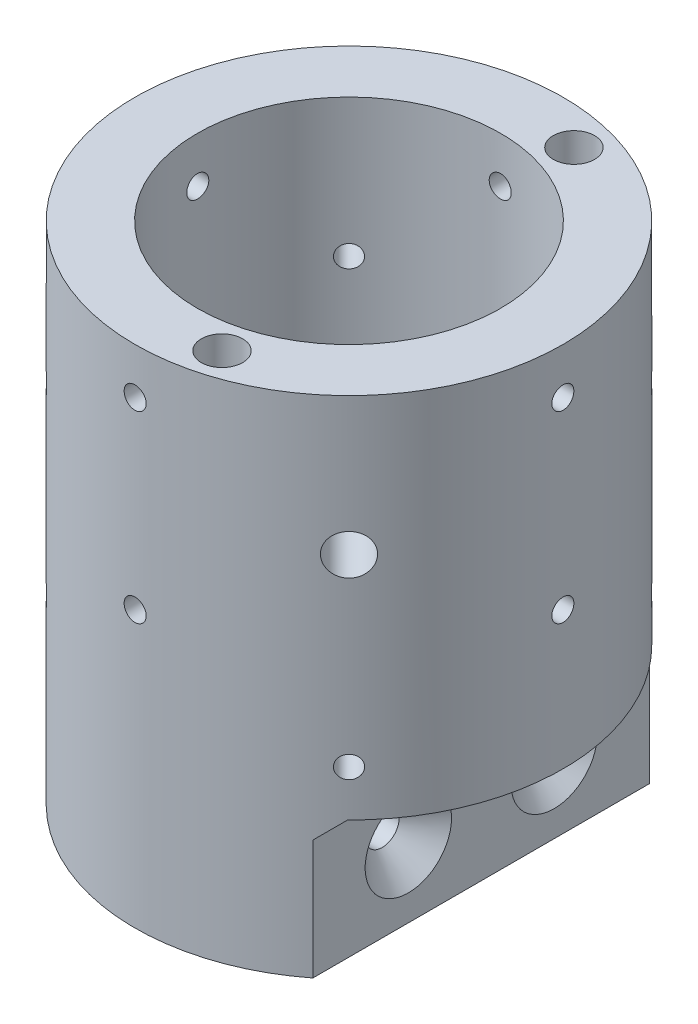
SolidWorks part; units mm, degrees
material "PLA плотность"
ref_plane "Спереди" through (0, 0, 0) normal (0, 0, 1) x (1, 0, 0)
ref_plane "Сверху" through (0, 0, 0) normal (0, 1, 0) x (1, 0, 0)
ref_plane "Справа" through (0, 0, 0) normal (1, 0, 0) x (0, 0, -1)
sketch "Эскиз1" plane through (0, 0, 0) normal (0, 1, 0) x (1, 0, 0)
  circle A0 centre (0, 0) radius 23.3
  dimension "D1" = 46.6
extrude "Бобышка-Вытянуть1" add sketch "Эскиз1" along normal blind 5
sketch "Эскиз2" plane through (0, 5, 0) normal (0, 1, 0) x (1, 0, 0)
  circle A0 centre (0, 0) radius 23.3
  circle A1 centre (0, 0) radius 16.5
  circle A2 centre (0, 0) radius 23.3 construction
  dimension "D1" = 33
  dimension "D2" = 0
extrude "Бобышка-Вытянуть2" add sketch "Эскиз2" along normal blind 35
chamfer "Фаска8" distance 2 angle 45 1 edges at (0, 5, 16.5)
sketch "Эскиз3" plane through (0, 0, 0) normal (1, 0, 0) x (0, 0, -1)
  line L0 (-23.3, 20) -> (28.0263, 20) construction
  line L1 (-23.3, 40) -> (-23.3, 0) construction
  line L2 (16.5, 40) -> (-16.5, 40) construction
  circle A1 centre (0, 35) radius 1.2
  dimension "D1" = 2.4
  dimension "D2" = 5
extrude "Вырез-Вытянуть1" cut sketch "Эскиз3" against normal through all
ref_plane "Плоскость1" through (0, 0, 0) normal (0.7071, 0, 0.7071) x (0, -1, 0)
sketch "Эскиз4" plane through (0, 0, 0) normal (0.7071, 0, 0.7071) x (0, -1, 0)
  line L0 (-20, 23.3) -> (-20, -30.0625) construction
  line L1 (0, 23.3) -> (-40, 23.3) construction
  line L3 (0, -23.3) -> (0, 23.3) construction
  circle A1 centre (-5, 0) radius 1.2
  dimension "D1" = 5
  dimension "D2" = 2.4
extrude "Вырез-Вытянуть2" cut sketch "Эскиз4" against normal through all from offset 16.3 offset against normal yes
pattern_circular "Круговой массив1" count 4 over 360 about axis through (0, 5, 0) along (0, -1, 0) of "Вырез-Вытянуть2"
pattern_circular "Круговой массив2" count 4 over 360 about axis through (0, 5, 0) along (0, -1, 0) of "Вырез-Вытянуть1"
pattern_linear "Линейный массив3" count 2 spacing 20 along (0, 1, 0) of "Круговой массив1"
pattern_linear "Линейный массив4" count 2 spacing 20 along (0, -1, 0) of "Круговой массив2"
sketch "Эскиз12" plane through (0, 0, 0) normal (0, -1, 0) x (1, 0, 0)
  line L1 (14.3923, 18.3235) -> (14.3923, -18.3235)
  line L20 (0, 15) -> (-2.7835, 17.7835)
  line L21 (-2.7835, -17.7835) -> (0, -15)
  line L22 (0, -15) -> (0, 15)
  line L23 (0, 15) -> (-2.7835, 17.7835)
  line L24 (-2.7835, -17.7835) -> (0, -15)
  line L25 (0, -15) -> (0, 15)
  circle A6 centre (0, 0) radius 23.3 construction
  arc A7 (14.3923, 18.3235) -> (14.3923, -18.3235) centre (0, 0) ccw
  arc A13 (-2.7835, 17.7835) -> (-2.7835, -17.7835) centre (0, 0) ccw
  arc A14 (-2.7835, 17.7835) -> (-2.7835, -17.7835) centre (0, 0) ccw
  dimension "D1" = 0
extrude "Бобышка-Вытянуть3" add sketch "Эскиз12" along normal blind 15 contours L1 region at (13.7929, 0, 0)
sketch "Эскиз13" plane through (0, -15, 0) normal (0, -1, 0) x (1, 0, 0)
  line L14 (-2.6786, -18.1029) -> (0.3, -15.1243)
  line L15 (0.3, 15.1243) -> (-2.6786, 18.1029)
  line L16 (0.3, -15.1243) -> (0.3, 15.1243)
  line L17 (-2.6786, -18.1029) -> (0.3, -15.1243)
  line L18 (0.3, 15.1243) -> (-2.6786, 18.1029)
  line L19 (0.3, -15.1243) -> (0.3, 15.1243)
  arc A5 (-2.6786, 18.1029) -> (-2.6786, -18.1029) centre (0, 0) ccw
  arc A6 (-2.6786, 18.1029) -> (-2.6786, -18.1029) centre (0, 0) ccw
  dimension "D1" = 0.3
extrude "Вырез-Вытянуть10" cut sketch "Эскиз13" against normal up to surface (15 mm away) up to face at (18.8461, 0, 0)
chamfer "Фаска4" distance 2 angle 45 1 edges at (14.3923, 0, 0)
chamfer "Фаска6" distance 2 angle 45 4 edges at (-1.1893, 0, -16.6136) (-18.3, 0, 0) (0.3, 0, 0) (-1.1893, 0, 16.6136)
chamfer "Фаска7" distance 2 angle 45 4 edges at (-1.1893, -15, -16.6136) (-18.3, -15, 0) (-1.1893, -15, 16.6136) (0.3, -15, 0)
hole_wizard "Зенковка для винта с полупотайной головкой M41" positions "Эскиз14" profile "Эскиз15" countersink size "M4" standard "ISO" end condition through all
sketch "Эскиз14" plane through (14.3923, -676.2045, -24.0267) normal (1, 0, 0) x (0, -0.1282, -0.9918)
  line L0 (-110.237, 665.565) -> (-108.5708, 652.6722) construction
  line L4 (-109.4039, 659.1186) -> (-20.4413, 659.1186) construction
  line L5 (-20.4413, 659.1186) -> (-1.8045, 659.1186) construction
  point P0 (-117.4039, 659.1186)
  point P19 (-101.6667, 661.1523)
sketch "Эскиз15" plane through (14.3923, -7.4747, 7.934) normal (0, 1, 0) x (0, 0, -1)
  line L0 (0, 0) -> (0, 37.6923)
  line L1 (0, 37.6923) -> (1.85, 37.6923)
  line L2 (1.85, 37.6923) -> (1.85, 2.85)
  line L3 (1.85, 2.85) -> (4.7, 0)
  line L4 (4.7, 0) -> (0, 0)
  line L5 (-1.85, 2.85) -> (-4.7, 0) construction
  line L6 (0, -6.35) -> (0, 107.95) construction
  dimension "Диаметр сквозного отверстия" = 3.7
  dimension "Глубина сквозного отверстия" = 37.6923
  dimension "Диаметр передней зенковки" = 9.4
  dimension "Угол передней зенковки" = 90
sketch "Эскиз17" plane through (0, -15, 0) normal (0, -1, 0) x (1, 0, 0)
  circle A0 centre (5.3288, 0) radius 2.5
extrude "Вырез-Вытянуть11" cut sketch "Эскиз17" against normal blind 86
ref_plane "Плоскость2" through (0, 0, 0) normal (-0.7071, 0, -0.7071) x (-0.7071, 0, 0.7071)
sketch "Эскиз18" plane through (0, 0, 0) normal (-0.7071, 0, -0.7071) x (-0.7071, 0, 0.7071)
  circle A0 centre (0, 25) radius 1.2 construction
  circle A1 centre (0, 25) radius 1.2
  circle A2 centre (0, 25) radius 2.2
extrude "Вырез-Вытянуть12" cut sketch "Эскиз18" against normal blind 86
sketch "Эскиз21" plane through (0, -15, 0) normal (0, -1, 0) x (1, 0, 0)
  line L0 (5.3288, -15.6158) -> (5.3288, -22.6825) construction
  circle A0 centre (5.3288, -19.1491) radius 2.25
  circle A1 centre (0, 0) radius 16.5 construction
  circle A2 centre (0, 0) radius 16.5 construction
  arc A3 (14.3923, 18.3235) -> (14.3923, -18.3235) centre (0, 0) ccw construction
  dimension "D1" = 4.5
extrude "Вырез-Вытянуть13" cut sketch "Эскиз21" against normal through all
mirror "Зеркальное отражение1" about plane through (0, 0, 0) normal (0, 0, 1) of "Вырез-Вытянуть13"
